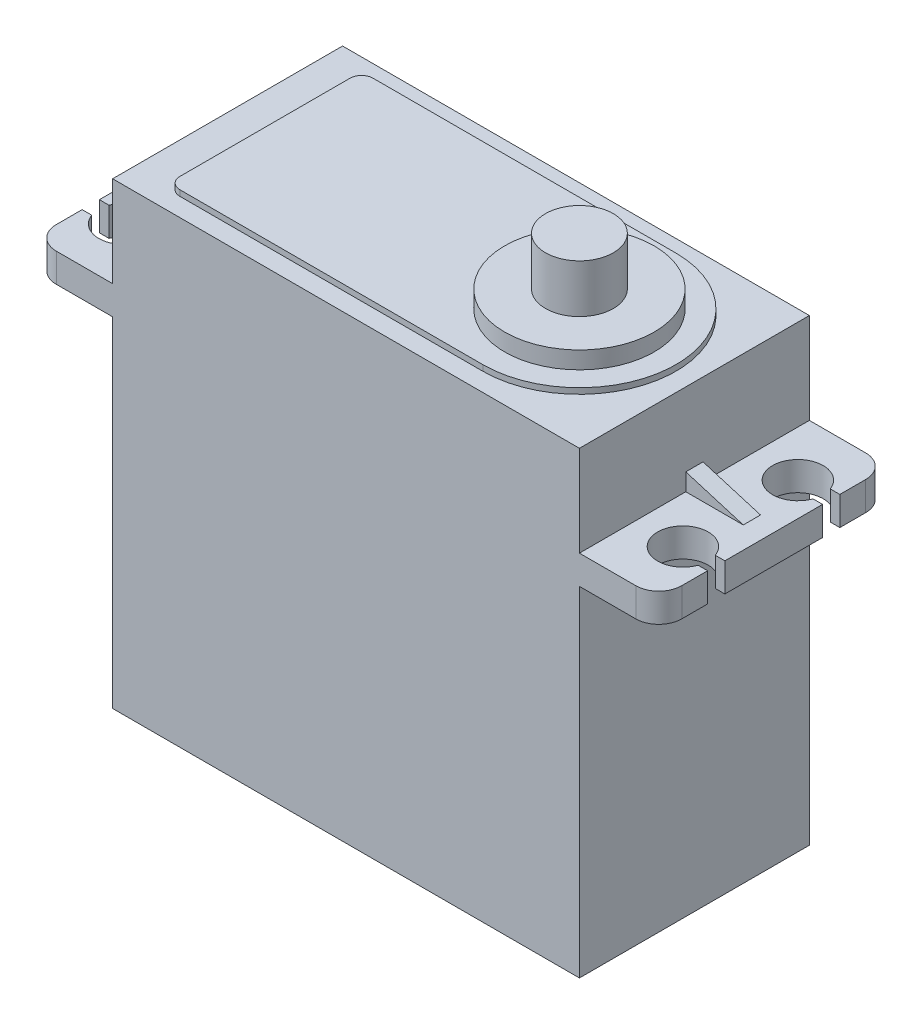
SolidWorks part; units mm, degrees
ref_plane "前视基准面" through (0, 0, 0) normal (0, 0, 1) x (1, 0, 0)
ref_plane "上视基准面" through (0, 0, 0) normal (0, 1, 0) x (1, 0, 0)
ref_plane "右视基准面" through (0, 0, 0) normal (1, 0, 0) x (0, 0, -1)
other "Configuration Table"
sketch "草图1" plane through (0, 0, 0) normal (0, 0, 1) x (1, 0, 0)
  line L0 (0, 11.6373) -> (0, 0) construction
  line L1 (-20.3, 19.95) -> (20.3, 19.95)
  line L3 (-20.3, -19.95) -> (20.3, -19.95)
  line L5 (0, 0) -> (12.3389, 0) construction
  line L20 (-20.3, 19.95) -> (-20.3, 12.05)
  line L21 (20.3, -19.95) -> (20.3, 9.55)
  line L22 (20.3, 12.05) -> (20.3, 19.95)
  line L23 (20.3, 12.05) -> (27.2, 12.05)
  line L25 (20.3, 9.55) -> (27.2, 9.55)
  line L26 (27.2, 12.05) -> (27.2, 9.55)
  line L27 (-27.2, 12.05) -> (-27.2, 9.55)
  line L28 (-20.3, 9.55) -> (-27.2, 9.55)
  line L29 (-20.3, 12.05) -> (-27.2, 12.05)
  line L30 (-20.3, 9.55) -> (-20.3, -19.95)
  dimension "D1" = 39.9
  dimension "D2" = 40.6
  dimension "D3" = 2.5
  dimension "D4" = 19.95
  dimension "D5" = 29.5
  dimension "D6" = 6.9
extrude "凸台-拉伸1" add sketch "草图1" along normal blind 10 and the other way blind 10
sketch "草图2" plane through (0, 12.05, 0) normal (0, 1, 0) x (1, 0, 0)
  line L0 (0, 4.5018) -> (0, 0) construction
  line L1 (0, 0) -> (6.1828, 0) construction
  line L2 (24.3, 5) -> (29.3503, 5) construction
  line L3 (26.3682, 4.25) -> (29.3503, 4.25)
  line L4 (26.3682, 5.75) -> (29.3503, 5.75)
  line L5 (29.3503, 5.75) -> (29.3503, 4.25)
  line L6 (26.3682, -4.25) -> (29.3503, -4.25)
  line L7 (24.3, 5.75) -> (29.3503, 5.75) construction
  line L8 (24.3, 4.25) -> (29.3503, 4.25) construction
  line L9 (29.3503, -5.75) -> (29.3503, -4.25)
  line L10 (26.3682, -5.75) -> (29.3503, -5.75)
  line L11 (-26.3682, -5.75) -> (-29.3503, -5.75)
  line L12 (-26.3682, -4.25) -> (-29.3503, -4.25)
  line L13 (-29.3503, -5.75) -> (-29.3503, -4.25)
  line L14 (-26.3682, 4.25) -> (-29.3503, 4.25)
  line L15 (-26.3682, 5.75) -> (-29.3503, 5.75)
  line L16 (-29.3503, 5.75) -> (-29.3503, 4.25)
  line L17 (20.3, 10) -> (20.3, -10) construction
  arc A0 (26.3682, 5.75) -> (26.3682, 4.25) centre (24.3, 5) ccw
  arc A1 (26.3682, -5.75) -> (26.3682, -4.25) centre (24.3, -5) cw
  arc A2 (-26.3682, -5.75) -> (-26.3682, -4.25) centre (-24.3, -5) ccw
  arc A3 (-26.3682, 5.75) -> (-26.3682, 4.25) centre (-24.3, 5) cw
  dimension "D1" = 4.4
  dimension "D2" = 5
  dimension "D3" = 24.3
  dimension "D6" = 48.6
  dimension "D7" = 4
  dimension "D4" = 0.75
  dimension "D5" = 0.75
extrude "切除-拉伸1" cut sketch "草图2" against normal blind 5
sketch "草图3" plane through (0, 19.95, 0) normal (0, 1, 0) x (1, 0, 0)
  line L0 (20.3, 10) -> (20.3, -10) construction
  line L1 (-16.05, 8.4) -> (10.3, 8.4)
  line L2 (-17.05, 7.4) -> (-17.05, -7.4)
  line L3 (-16.05, -8.4) -> (10.3, -8.4)
  line L5 (20.3, -10) -> (-20.3, -10) construction
  arc A0 (10.3, -8.4) -> (10.3, 8.4) centre (10.3, 0) ccw
  arc A1 (-16.05, -8.4) -> (-17.05, -7.4) centre (-16.05, -7.4) cw
  arc A2 (-17.05, 7.4) -> (-16.05, 8.4) centre (-16.05, 7.4) cw
  point P5 (-17.05, -8.4)
  point P17 (-17.05, 8.4)
  dimension "D1" = 16.8
  dimension "D2" = 10
  dimension "D5" = 0
  dimension "D7" = 1
  dimension "D3" = 16.8
  dimension "D4" = 1.6
extrude "凸台-拉伸2" add sketch "草图3" along normal blind 0.5
sketch "草图4" plane through (0, 20.45, 0) normal (0, 1, 0) x (1, 0, 0)
  circle A0 centre (10.3, 0) radius 6.5
extrude "凸台-拉伸3" add sketch "草图4" along normal blind 1.5
sketch "草图5" plane through (0, 21.95, 0) normal (0, 1, 0) x (1, 0, 0)
  line L0 (10.3, 0) -> (10.3, 2.95) construction
  circle A0 centre (10.3, 0) radius 2.95
extrude "凸台-拉伸4" add sketch "草图5" along normal blind 4.2
fillet "圆角1" radius 2 4 edges at (-27.2, 10.8, 10) (-27.2, 10.8, -10) (27.2, 10.8, -10) (27.2, 10.8, 10)
sketch "草图8" plane through (0, 0, 0) normal (0, 0, 1) x (1, 0, 0)
  line L0 (20.3, 13.55) -> (20.3, 12.05)
  line L1 (20.3, 12.05) -> (20.3, 19.95) construction
  line L2 (20.3, 12.05) -> (25.3, 12.05)
  line L3 (25.2, 12.05) -> (20.3, 12.05) construction
  line L4 (25.3, 12.05) -> (20.3, 13.55)
  dimension "D1" = 5
  dimension "D2" = 1.5
extrude "凸台-拉伸5" add sketch "草图8" along normal blind 0.75 and the other way blind 0.75
mirror "镜向1" about plane through (0, 0, 0) normal (1, 0, 0) of "凸台-拉伸5"
sketch "草图9" plane through (0, 26.15, 0) normal (0, 1, 0) x (1, 0, 0)
  line L0 (10.3, 0) -> (20.3, 0) construction
  line L1 (20.3, 10) -> (20.3, -10) construction
  line L2 (24.3, -5) -> (20.3, -5) construction
  line L3 (20.3, -0.75) -> (20.3, -10) construction
  line L4 (24.3, -5) -> (27.25, -5) construction
  line L5 (-27.2, 0) -> (27.2, 0) construction
  line L6 (-27.2, 4.25) -> (-27.2, -4.25) construction
  line L7 (27.2, 4.25) -> (27.2, -4.25) construction
  line L8 (-27.2, -5.75) -> (-20.3, -5.75) construction
  line L9 (-20.3, -0.75) -> (-20.3, -10) construction
  line L10 (-20.3, 4.7411) -> (20.3, 4.7411) construction
  line L11 (-20.3, 10) -> (-20.3, 0.75) construction
  line L12 (20.3, 10) -> (20.3, 0.75) construction
  arc A0 (-26.3682, 4.25) -> (-26.3682, 5.75) centre (-24.3, 5) ccw construction
  dimension "D1" = 34.6
sketch "草图10" plane through (0, 0, 10) normal (0, 0, 1) x (1, 0, 0)
  line L0 (20.3, 12.05) -> (20.3, 19.95) construction
  line L1 (20.3, 19.95) -> (20.3, 26.15) construction
  line L2 (24.3, 26.15) -> (20.3, 26.15) construction
  line L3 (10.3, 26.15) -> (20.3, 26.15) construction
  line L4 (10.3, 20.45) -> (10.3, 26.15) construction
sketch "草图11" plane through (0, 19.95, 0) normal (0, 1, 0) x (1, 0, 0)
  line L0 (24.3, 5) -> (20.3, 5) construction
  line L1 (20.3, 10) -> (20.3, 0.75) construction
  line L2 (-24.3, 5) -> (-20.3, 5) construction
  line L3 (-20.3, 10) -> (-20.3, -10) construction
